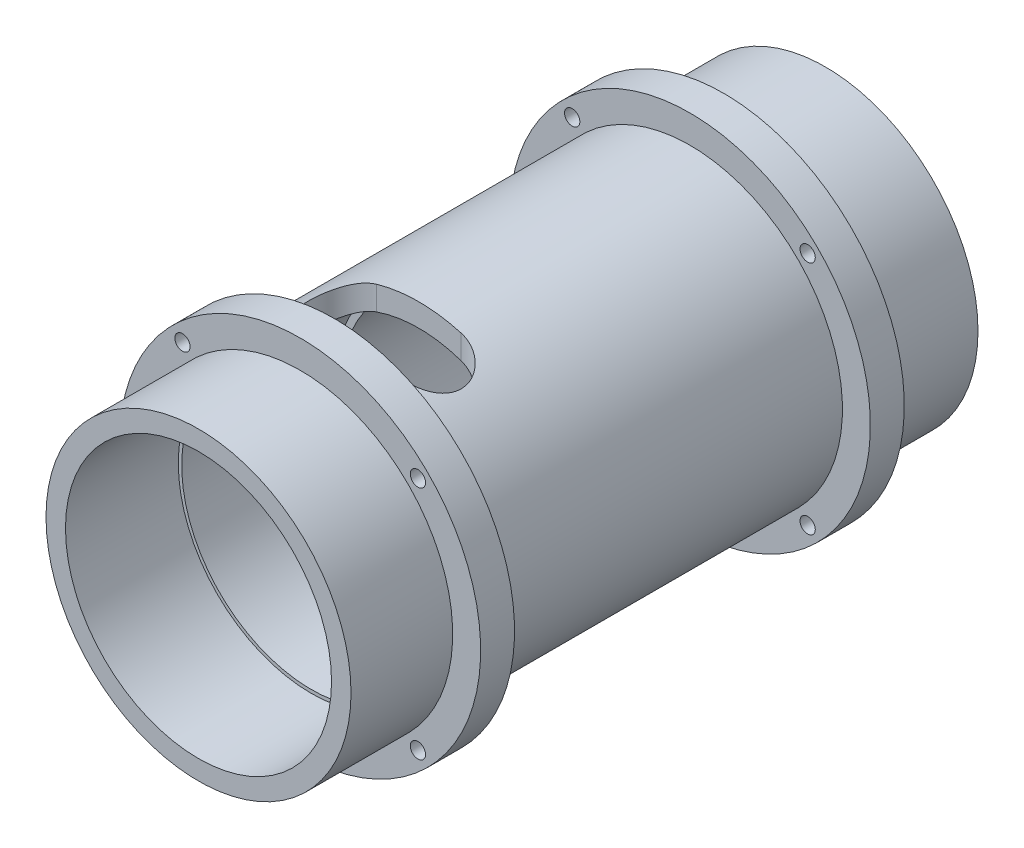
SolidWorks part; units mm, degrees
material "6061-T6 (SS)"
ref_plane "Front Plane" through (0, 0, 0) normal (0, 0, 1) x (1, 0, 0)
ref_plane "Top Plane" through (0, 0, 0) normal (0, 1, 0) x (1, 0, 0)
ref_plane "Right Plane" through (0, 0, 0) normal (1, 0, 0) x (0, 0, -1)
sketch "Sketch1" plane through (0, 0, 0) normal (0, 0, 1) x (1, 0, 0)
  circle A0 centre (0, 0) radius 33.75
  circle A1 centre (0, 0) radius 45
  dimension "D1" = 67.5
  dimension "D2" = 90
extrude "Boss-Extrude1" add sketch "Sketch1" along normal mid plane 185
sketch "Sketch2" plane through (0, 0, 0) normal (0, 1, 0) x (1, 0, 0)
  line L0 (0, -92.5) -> (0, 92.5)
  line L1 (-45, -92.5) -> (45, -92.5) construction
  line L2 (33.75, 92.5) -> (-33.75, 92.5) construction
  line L3 (0, -92.5) -> (-39.25, -92.5)
  line L4 (-39.25, -92.5) -> (-39.25, -59.2129)
  line L5 (-39.25, -59.2129) -> (-38.25, -59.2129)
  line L6 (-38.25, -59.2129) -> (-38.25, -13.85)
  line L7 (-38.25, -13.85) -> (-36.25, -13.85)
  line L8 (-36.25, -13.85) -> (-36.25, 86.15)
  line L9 (-36.25, 86.15) -> (-38.25, 86.15)
  line L10 (-38.25, 86.15) -> (-38.25, 92.5)
  line L11 (-38.25, 92.5) -> (0, 92.5)
  dimension "D1" = 39.25
  dimension "D2" = 33.2871
  dimension "D3" = 38.25
  dimension "D4" = 78.65
  dimension "D5" = 178.65
  dimension "D6" = 36.25
revolve "Cut-Revolve1" cut sketch "Sketch2" angle 360 about L0
sketch "Sketch4" plane through (0, 0, 0) normal (1, 0, 0) x (0, 0, -1)
  line L0 (-62.5, 45) -> (-62.5, 53.25)
  line L1 (92.5, 45) -> (-92.5, 45) construction
  line L2 (-62.5, 53.25) -> (-52.5, 53.25)
  line L3 (-52.5, 53.25) -> (-52.5, 45)
  line L4 (-52.5, 45) -> (-62.5, 45)
  line L5 (-92.5, 45) -> (-92.5, -45) construction
  line L7 (0, 0) -> (0, 45) construction
  line L8 (92.5, 45) -> (-92.5, 45) construction
  line L9 (52.5, 53.25) -> (52.5, 45)
  line L10 (62.5, 53.25) -> (52.5, 53.25)
  line L11 (62.5, 45) -> (62.5, 53.25)
  line L12 (52.5, 45) -> (62.5, 45)
  line L13 (92.5, 0) -> (-92.5, 0) construction
  line L14 (92.5, -45) -> (92.5, 45) construction
  dimension "D1" = 30
  dimension "D2" = 8.25
  dimension "D3" = 10
revolve "Revolve1" add sketch "Sketch4" angle 360 about L13
sketch "Sketch7" plane through (0, 0, 62.5) normal (0, 0, 1) x (1, 0, 0)
  line L0 (0, 45) -> (0, 53.25) construction
  line L1 (0, 0) -> (49.125, 0) construction
  line L2 (0, 0) -> (-34.7366, 34.7366) construction
  circle A0 centre (0, 0) radius 45 construction
  circle A1 centre (0, 0) radius 53.25 construction
  circle A2 centre (0, 0) radius 49.125 construction
  point P10 (0, 49.125)
  point P11 (-34.7366, 34.7366)
  point P13 (34.7366, 34.7366)
  point P14 (-34.7366, -34.7366)
  point P16 (34.7366, -34.7366)
  dimension "D1" = 45
hole_wizard "M4 Clearance Hole1" positions "Sketch7" profile "Sketch8" hole size "M4" standard "ANSI Metric" end condition through all
sketch "Sketch8" plane through (34.7366, -34.7366, 62.5) normal (1, 0, 0) x (0, -1, 0)
  line L0 (0, 0) -> (0, 155)
  line L1 (0, 155) -> (2.25, 155)
  line L2 (2.25, 155) -> (2.25, 0)
  line L5 (2.25, 0) -> (0, 0)
  line L11 (0, -6.35) -> (0, 107.95) construction
  dimension "Thru Hole Dia." = 4.5
  dimension "Thru Hole Depth" = 155
sketch "Sketch3" plane through (0, 0, 0) normal (0, 1, 0) x (1, 0, 0)
  line L0 (-12.5, -37.5) -> (12.5, -37.5) construction
  line L1 (-12.5, -27.5) -> (12.5, -27.5)
  line L2 (-12.5, -47.5) -> (12.5, -47.5)
  line L5 (-45, -92.5) -> (45, -92.5) construction
  arc A0 (-12.5, -27.5) -> (-12.5, -47.5) centre (-12.5, -37.5) ccw
  arc A1 (12.5, -47.5) -> (12.5, -27.5) centre (12.5, -37.5) ccw
  point P2 (0, -37.5)
  dimension "D3" = 10
  dimension "D1" = 55
  dimension "D2" = 25
extrude "Cut-Extrude1" cut sketch "Sketch3" along normal through all
